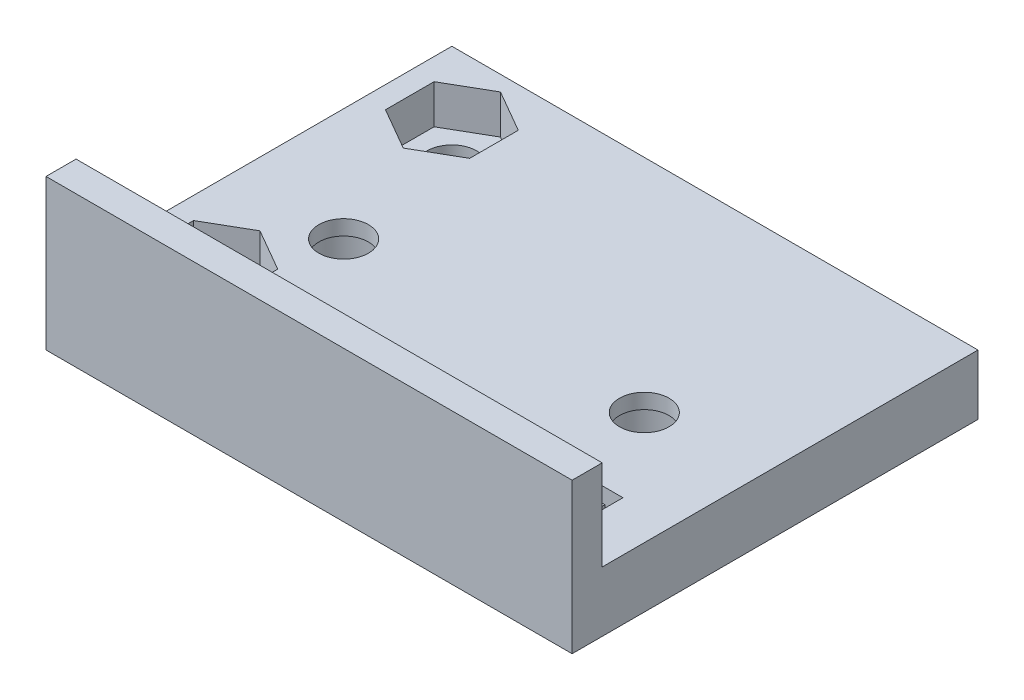
SolidWorks part; units mm, degrees
ref_plane "Front Plane" through (0, 0, 0) normal (0, 0, 1) x (1, 0, 0)
ref_plane "Top Plane" through (0, 0, 0) normal (0, 1, 0) x (1, 0, 0)
ref_plane "Right Plane" through (0, 0, 0) normal (1, 0, 0) x (0, 0, -1)
sketch "Sketch3" plane through (0, 0, 0) normal (0, 1, 0) x (1, 0, 0)
  line L0 (-17.5, -11.5) -> (17.5, -11.5) construction
  line L1 (-17.5, -13.5) -> (17.5, -13.5)
  line L2 (-17.5, -13.5) -> (-17.5, 13.5)
  line L3 (-17.5, 13.5) -> (17.5, 13.5)
  line L4 (17.5, -13.5) -> (17.5, 13.5)
  line L5 (-17.5, -13.5) -> (17.5, 13.5) construction
  line L6 (-17.5, 13.5) -> (17.5, -13.5) construction
  line L7 (0, 13.5) -> (0, -13.5) construction
  circle A0 centre (10, -1.2) radius 1.65
  circle A1 centre (-10, -1.2) radius 1.65
  point P0 (0, 0)
  dimension "D6" = 3.3
  dimension "D1" = 35
  dimension "D2" = 27
  dimension "D3" = 25
  dimension "D4" = 10.3
  dimension "D5" = 7.5
extrude "Boss-Extrude2" add sketch "Sketch3" along normal blind 4
sketch "Sketch5" plane through (0, 4, 0) normal (0, 1, 0) x (1, 0, 0)
  line L0 (-17.5, -11.5) -> (17.5, -11.5)
  line L1 (-17.5, 13.5) -> (-17.5, -13.5) construction
  line L2 (17.5, -13.5) -> (17.5, 13.5) construction
  line L3 (17.5, -11.5) -> (17.5, -13.5)
  line L4 (17.5, -13.5) -> (-17.5, -13.5)
  line L5 (-17.5, -13.5) -> (-17.5, -11.5)
  line L6 (17.5, 13.5) -> (-17.5, 13.5) construction
  dimension "D1" = 25
extrude "Boss-Extrude3" add sketch "Sketch5" along normal blind 6
sketch "Sketch7" plane through (0, 0, 0) normal (0, -1, 0) x (1, 0, 0)
  line L0 (0.25, -1.25) -> (-15.5, -1.25) construction
  line L1 (-15.5, -11.5) -> (0.25, -11.5) construction
  line L2 (-15.5, -11.5) -> (-15.5, 9) construction
  line L3 (-15.5, 9) -> (0.25, 9) construction
  line L4 (0.25, -11.5) -> (0.25, 9) construction
  line L5 (17.5, -13.5) -> (-17.5, -13.5) construction
  line L6 (-17.5, -13.5) -> (-17.5, 13.5) construction
  circle A0 centre (-13.25, -9.25) radius 1.65
  circle A1 centre (-13.25, 6.75) radius 1.65
  point P8 (-10.0021, -8.5153)
  dimension "D7" = 3.3
  dimension "D1" = 15.75
  dimension "D2" = 20.5
  dimension "D3" = 2.25
  dimension "D4" = 2.25
  dimension "D5" = 2
  dimension "D6" = 2
extrude "Cut-Extrude2" cut sketch "Sketch7" against normal up to surface (4 mm away) up to face at (-10, 4, -0.45)
sketch "Sketch8" plane through (0, 4, 0) normal (0, 1, 0) x (1, 0, 0)
  line L1 (-10.45, 7.6334) -> (-10.45, 10.8666)
  line L2 (-10.45, 10.8666) -> (-13.25, 12.4832)
  line L3 (-13.25, 12.4832) -> (-16.05, 10.8666)
  line L4 (-16.05, 10.8666) -> (-16.05, 7.6334)
  line L5 (-16.05, 7.6334) -> (-13.25, 6.0168)
  line L6 (-13.25, 6.0168) -> (-10.45, 7.6334)
  line L7 (-10.45, -5.1334) -> (-13.25, -3.5168)
  line L8 (-13.25, -3.5168) -> (-16.05, -5.1334)
  line L9 (-16.05, -5.1334) -> (-16.05, -8.3666)
  line L10 (-16.05, -8.3666) -> (-13.25, -9.9832)
  line L11 (-13.25, -9.9832) -> (-10.45, -8.3666)
  line L12 (-10.45, -8.3666) -> (-10.45, -5.1334)
  circle A0 centre (-13.25, 9.25) radius 2.8 construction
  circle A1 centre (-13.25, -6.75) radius 2.8 construction
  point P10 (-14.1657, -3.6011)
  dimension "D1" = 5.6
extrude "Cut-Extrude3" cut sketch "Sketch8" against normal blind 2.6
sketch "Sketch9" plane through (0, 0, 0) normal (0, -1, 0) x (1, 0, 0)
  circle A0 centre (-10, 1.2) radius 2.7
  circle A1 centre (10, 1.2) radius 2.7
  dimension "D1" = 5.4
extrude "Cut-Extrude4" cut sketch "Sketch9" against normal blind 3
sketch "Sketch10" plane through (0, 0, 0) normal (0, -1, 0) x (1, 0, 0)
  line L0 (10, 13.5) -> (10, 1.2) construction
  line L1 (-17.5, 13.5) -> (17.5, 13.5) construction
  line L2 (7, 6.8191) -> (7, 9.6191)
  line L3 (14.2, 6.8191) -> (13, 6.8191)
  line L4 (14.2, 6.8191) -> (14.2, 9.6191)
  line L5 (14.2, 9.6191) -> (13, 9.6191)
  line L6 (13, 6.8191) -> (13, 9.6191)
  line L7 (14.2, 6.8191) -> (13, 9.6191) construction
  line L8 (14.2, 9.6191) -> (13, 6.8191) construction
  line L9 (5.8, 9.6191) -> (7, 9.6191)
  line L10 (5.8, 6.8191) -> (5.8, 9.6191)
  line L11 (5.8, 6.8191) -> (7, 6.8191)
  point P4 (13.6, 8.2191)
  point P9 (10, 1.2)
  dimension "D1" = 1.2
  dimension "D2" = 2.8
  dimension "D3" = 3.8809
  dimension "D4" = 6
extrude "Cut-Extrude5" cut sketch "Sketch10" against normal up to surface (4 mm away) up to face at (-13.25, 4, -9.25)
sketch "Sketch11" plane through (0, 4, 0) normal (0, 1, 0) x (1, 0, 0)
  line L0 (7, -6.8191) -> (13, -6.8191)
  line L1 (13, -6.8191) -> (13, -9.6191)
  line L2 (13, -9.6191) -> (7, -9.6191)
  line L3 (7, -9.6191) -> (7, -6.8191)
extrude "Cut-Extrude6" cut sketch "Sketch11" against normal blind 1
